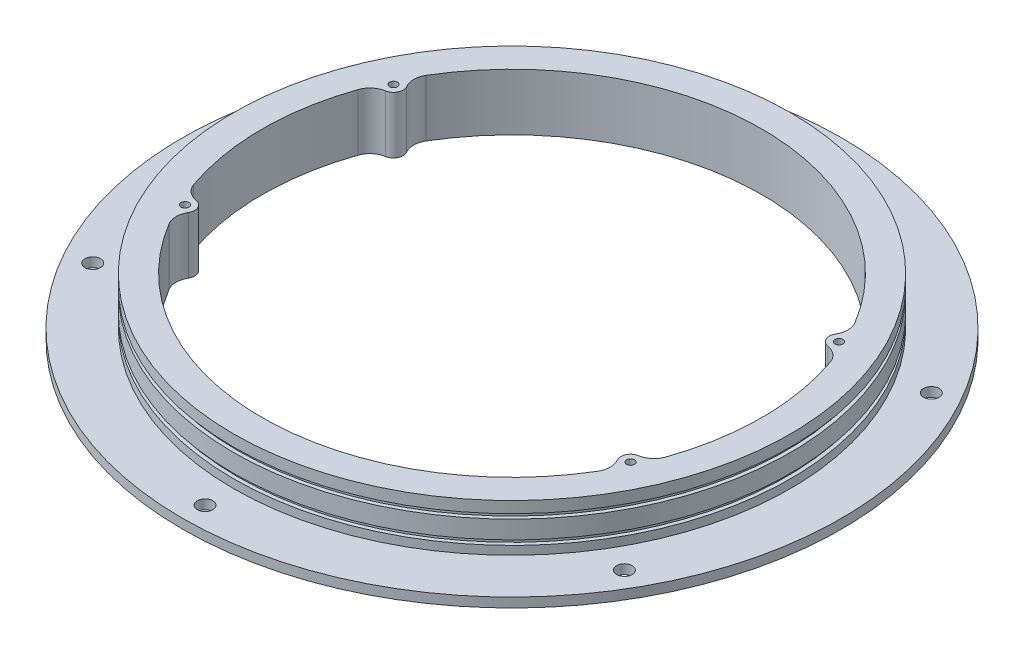
SolidWorks part; units mm, degrees
ref_plane "Front Plane" through (0, 0, 0) normal (0, 0, 1) x (1, 0, 0)
ref_plane "Top Plane" through (0, 0, 0) normal (0, 1, 0) x (1, 0, 0)
ref_plane "Right Plane" through (0, 0, 0) normal (1, 0, 0) x (0, 0, -1)
sketch "Sketch1" plane through (0, 0, 0) normal (0, 1, 0) x (1, 0, 0)
  line L0 (0, 150) -> (0, 173.85) construction
  line L1 (-117.5162, 55) -> (-117.5162, -55) construction
  line L6 (-117.5162, -55) -> (117.5162, -55) construction
  line L7 (117.5162, -55) -> (117.5162, 55) construction
  line L8 (117.5162, 55) -> (-117.5162, 55) construction
  line L9 (-117.5162, 55) -> (117.5162, -55) construction
  circle A0 centre (0, 0) radius 146.85
  circle A1 centre (0, 0) radius 173.85
  circle A2 centre (0, 0) radius 131.85
  circle A3 centre (0, 0) radius 144.85
  circle A4 centre (0, 161.925) radius 4.1
  circle A5 centre (140.2312, 80.9625) radius 4.1
  circle A6 centre (140.2312, -80.9625) radius 4.1
  circle A7 centre (0, -161.925) radius 4.1
  circle A8 centre (-140.2312, -80.9625) radius 4.1
  circle A9 centre (-140.2312, 80.9625) radius 4.1
  circle A10 centre (0, 0) radius 150 construction
  circle A11 centre (-117.5162, 55) radius 2.1
  circle A12 centre (-117.5162, -55) radius 2.1
  circle A13 centre (117.5162, -55) radius 2.1
  circle A14 centre (117.5162, 55) radius 2.1
  arc A15 (-113.1213, 57.5874) -> (-116.6874, 49.9678) centre (-117.5162, 55) cw
  arc A16 (-116.6874, -49.9678) -> (-113.1213, -57.5874) centre (-117.5162, -55) cw
  arc A17 (116.6874, -49.9678) -> (113.1213, -57.5874) centre (117.5162, -55) ccw
  arc A18 (113.1213, 57.5874) -> (116.6874, 49.9678) centre (117.5162, 55) ccw
  arc A19 (116.6874, 49.9678) -> (124.5054, 43.3917) centre (115.0624, 40.1007) cw
  arc A20 (113.1213, 57.5874) -> (113.0803, 67.8032) centre (104.5038, 62.6608) ccw
  arc A21 (113.1213, -57.5874) -> (113.0803, -67.8032) centre (104.5038, -62.6608) cw
  arc A22 (116.6874, -49.9678) -> (124.5054, -43.3917) centre (115.0624, -40.1007) ccw
  arc A23 (-113.1213, -57.5874) -> (-113.0803, -67.8032) centre (-104.5038, -62.6608) ccw
  arc A24 (-116.6874, -49.9678) -> (-124.5054, -43.3917) centre (-115.0624, -40.1007) cw
  arc A25 (-113.1213, 57.5874) -> (-113.0803, 67.8032) centre (-104.5038, 62.6608) cw
  arc A26 (-116.6874, 49.9678) -> (-124.5054, 43.3917) centre (-115.0624, 40.1007) ccw
  point P23 (0, 0)
  point P54 (0, 0)
  point P55 (122.7908, 48.0297)
  dimension "D1" = 293.7
  dimension "D5" = 8.2
  dimension "D7" = 300
  dimension "D8" = 4.2
  dimension "D11" = 10
  dimension "D2" = 27
  dimension "D3" = 15
  dimension "D4" = 2
  dimension "D9" = 110
  dimension "D10" = 3
  dimension "D6" = 6
extrude "Boss-Extrude1" add sketch "Sketch1" along normal blind 5 contours A3 A2 | A0 A3 | A1 A4 A0 region at (-146.4346, 0, 0) region at (-168.9328, 0, 0) region at (-140.753, 0, 0)
extrude "Boss-Extrude2" add sketch "Sketch1<3>" along normal blind 30 contours A3 A2 | A0 A3 | A16 A24 A2 A12 A23 | A22 A17 A21 A2 A13 | A20 A18 A19 A2 A14 | A26 A15 A25 A2 A11 region at (-146.4346, 0, 0) region at (121.6749, 0, -47.9619) region at (121.8695, 0, 49.6034) region at (-114.7762, 0, -62.7021) region at (-116.1612, 0, 61.7999) region at (-140.753, 0, 0)
sketch "Sketch1<3>" plane through (0, 0, 0) normal (0, 1, 0) x (1, 0, 0) same geometry as "Sketch1"
cosmetic thread "Cosmetic Thread1" parameters "D2"=5
cosmetic thread "Cosmetic Thread2" parameters "D2"=5
cosmetic thread "Cosmetic Thread3" parameters "D2"=5
cosmetic thread "Cosmetic Thread4" parameters "D2"=5
extrude "Cut-Extrude1" cut sketch "Sketch1<4>" against normal blind 2.5 from offset 12 contours A0 A3 region at (-146.4346, 0, 0)
sketch "Sketch1<4>" plane through (0, 0, 0) normal (0, 1, 0) x (1, 0, 0) same geometry as "Sketch1"
extrude "Cut-Extrude2" cut sketch "Sketch1<5>" against normal blind 2.5 from offset 24 contours A0 A3 region at (-146.4346, 0, 0)
sketch "Sketch1<5>" plane through (0, 0, 0) normal (0, 1, 0) x (1, 0, 0) same geometry as "Sketch1"
equation "\"acTubeOD\"= 300mm"
equation "\"acTubeThickness\"= 3mm"
equation "\"acTubeLength\"= 300mm"
equation "\"threadedRodDiam\"= 8mm"
equation "\"D1@Sketch1\"=\"acTubeOD\"-\"acTubeThickness\"*2-0.3"
equation "\"D2@Sketch1\" = \"acTubeThickness\" + \"flange width\""
equation "\"D5@Sketch1\" = \"threadedRodDiam\" + 0.2"
equation "\"D7@Sketch1\"=\"acTubeOD\""
equation "\"flange width\"= 24mm"
